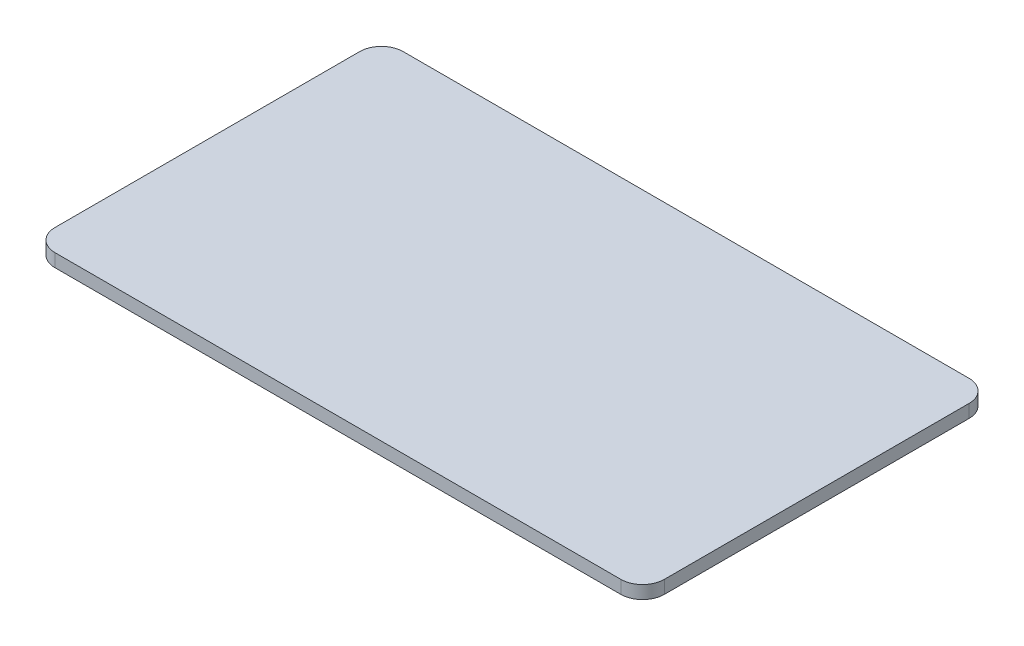
SolidWorks part; units mm, degrees
ref_plane "Спереди" through (0, 0, 0) normal (0, 0, 1) x (1, 0, 0)
ref_plane "Сверху" through (0, 0, 0) normal (0, 1, 0) x (1, 0, 0)
ref_plane "Справа" through (0, 0, 0) normal (1, 0, 0) x (0, 0, -1)
sketch "Эскиз1" plane through (0, 0, 0) normal (0, 1, 0) x (1, 0, 0)
  line L1 (35, -20) -> (-35, -20)
  line L2 (35, -20) -> (35, 20)
  line L3 (35, 20) -> (-35, 20)
  line L4 (-35, -20) -> (-35, 20)
  line L5 (35, -20) -> (-35, 20) construction
  line L6 (35, 20) -> (-35, -20) construction
  point P0 (0, 0)
  dimension "D1" = 70
  dimension "D2" = 40
extrude "Бобышка-Вытянуть1" add sketch "Эскиз1" along normal blind 1.5
fillet "Скругление1" radius 2.5 4 edges at (-35, 0.75, -20) (35, 0.75, -20) (35, 0.75, 20) (-35, 0.75, 20)
